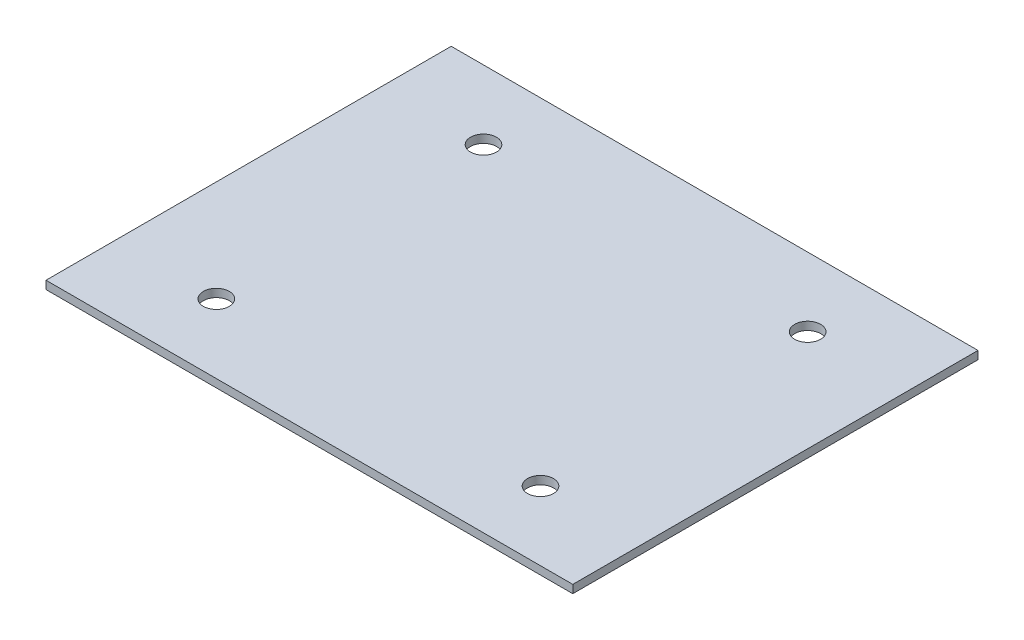
SolidWorks part; units mm, degrees
ref_plane "Спереди" through (0, 0, 0) normal (0, 0, 1) x (1, 0, 0)
ref_plane "Сверху" through (0, 0, 0) normal (0, 1, 0) x (1, 0, 0)
ref_plane "Справа" through (0, 0, 0) normal (1, 0, 0) x (0, 0, -1)
sketch "Эскиз1" plane through (0, 0, 0) normal (0, 1, 0) x (1, 0, 0)
  line L0 (105, 17.0342) -> (25, 17.0342) construction
  line L5 (0, 0) -> (130, 0)
  line L6 (0, 0) -> (0, 100)
  line L7 (0, 100) -> (130, 100)
  line L8 (130, 0) -> (130, 100)
  line L9 (130, 50) -> (0, 50) construction
  circle A0 centre (105, 17.0342) radius 3.2
  circle A1 centre (25, 17.0342) radius 3.2
  circle A2 centre (105, 82.9658) radius 3.2
  circle A3 centre (25, 82.9658) radius 3.2
  dimension "D1" = 130
  dimension "D2" = 100
extrude "Бобышка-Вытянуть1" add sketch "Эскиз1" along normal blind 2
